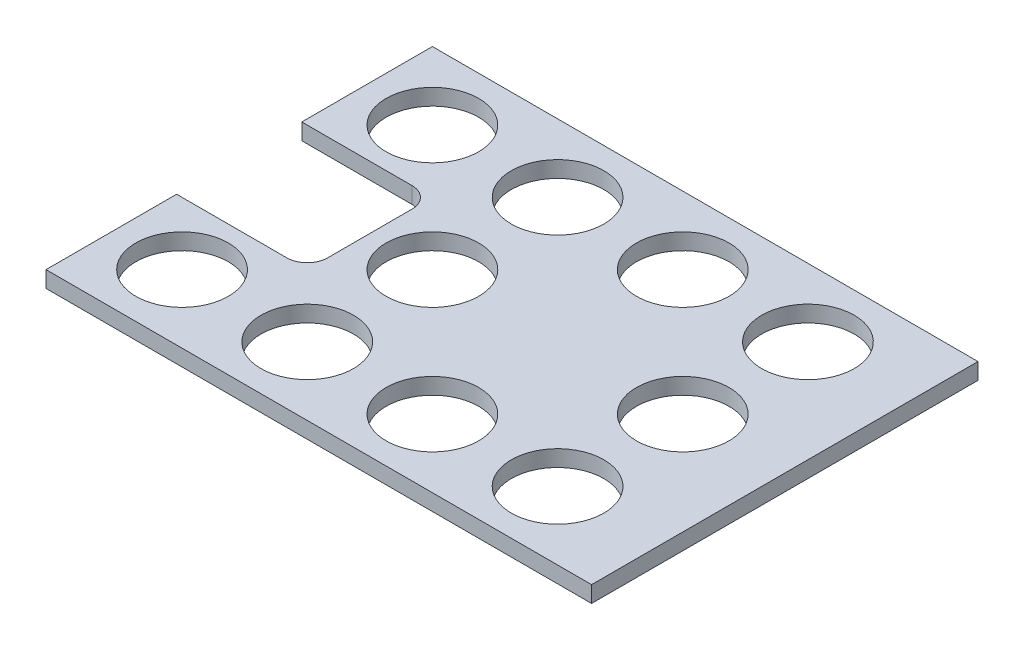
SolidWorks part; units mm, degrees
material "Pine"
ref_plane "Front Plane" through (0, 0, 0) normal (0, 0, 1) x (1, 0, 0)
ref_plane "Top Plane" through (0, 0, 0) normal (0, 1, 0) x (1, 0, 0)
ref_plane "Right Plane" through (0, 0, 0) normal (1, 0, 0) x (0, 0, -1)
sketch "Sketch1" plane through (0, 0, 0) normal (0, 1, 0) x (1, 0, 0)
  line L0 (50, 50) -> (268.076, 50) construction
  line L1 (0, 0) -> (401, 0)
  line L2 (0, 0) -> (0, 284)
  line L3 (0, 284) -> (401, 284)
  line L4 (401, 0) -> (401, 284)
  line L6 (0, 188) -> (81, 188)
  line L7 (0, 188) -> (0, 96)
  line L8 (0, 96) -> (81, 96)
  line L9 (96, 173) -> (96, 111)
  circle A0 centre (50, 50) radius 34
  circle A1 centre (50, 234) radius 34
  arc A2 (81, 96) -> (96, 111) centre (81, 111) ccw
  arc A3 (81, 188) -> (96, 173) centre (81, 173) cw
  circle A4 centre (142, 142) radius 34
  circle A5 centre (326, 142) radius 34
  point P21 (40.5, 96)
  point P22 (96, 142)
  dimension "D2" = 68
  dimension "D9" = 15
  dimension "D1" = 50
  dimension "D3" = 401
  dimension "height" = 284
  dimension "middle" = 142
  dimension "D12" = 142
  dimension "D4" = 92
  dimension "D10" = 96
  dimension "D8" = 96
  dimension "D7" = 50
  dimension "D11" = 46
  dimension "D6" = 46
  dimension "D5" = 46
  dimension "D13" = 184
extrude "Boss-Extrude1" add sketch "Sketch1" along normal blind 12 contours L2 L3 L4 L1
extrude "Cut-Extrude1" cut sketch "Sketch1<3>" along normal up to surface (12 mm away) contours A0 | A1 up to face at (200.5, 12, -142)
sketch "Sketch1<3>" plane through (0, 0, 0) normal (0, 1, 0) x (1, 0, 0) same geometry as "Sketch1"
pattern_linear "LPattern1" count 4 spacing 92 along (1, 0, 0) of "Cut-Extrude1"
extrude "Cut-Extrude3" cut sketch "Sketch1<4>" along normal up to surface (12 mm away) contours A3 L6 L2 L8 A2 L9 | A4 | A5 region at (47.5064, 0, -142) region at (142, 0, -142) region at (326, 0, -142) up to face at (326, 12, -16)
sketch "Sketch1<4>" plane through (0, 0, 0) normal (0, 1, 0) x (1, 0, 0) same geometry as "Sketch1"
equation "\"LENGTH\" = 1000mm"
equation "\"PLY\"= 12mm"
equation "\"D1@Boss-Extrude1\"=\"PLY\""
equation "\"CENTER_BRACE_LENGTH\" = 393mm"
equation "\"D3@Sketch1\"=\"CENTER_BRACE_LENGTH\" + \"HOUSING_DEPTH\" * 2"
equation "\"WIDTH\" = 300mm"
equation "\"HEIGHT\" = 300mm"
equation "\"HOUSING_DEPTH\" = 4mm"
equation "\"PANEL_WIDTH\"= \"LENGTH\" - \"CENTER_BRACE_LENGTH\" * 2 - \"PLY\" * 4"
equation "\"PANEL_SMALL_HEIGHT\" = 70mm"
equation "\"PORT_WIDTH\" = 90mm"
equation "\"PORT_RADIUS\" = 15mm"
equation "\"PORT_BRACE_HEIGHT\" = 92mm"
equation "\"DOWEL_SIZE\" = 0.25in"
equation "\"DOWEL_OFFSET\" = 30mm"
equation "\"height@Sketch1\" = \"HEIGHT\" - \"PLY\" * 2 + \"HOUSING_DEPTH\" * 2"
equation "\"middle@Sketch1\" = \"height@Sketch1\" / 2"
equation "\"D12@Sketch1\" = \"middle@Sketch1\""
equation "\"D4@Sketch1\"=\"PORT_BRACE_HEIGHT\""
equation "\"D10@Sketch1\"=\"height@Sketch1\" / 2 - \"PORT_BRACE_HEIGHT\" / 2"
equation "\"D8@Sketch1\"=\"PORT_BRACE_HEIGHT\" + \"HOUSING_DEPTH\""
equation "\"cut_out_offset\"= 46mm"
equation "\"D7@Sketch1\"=\"cut_out_offset\" + \"HOUSING_DEPTH\""
equation "\"D1@Sketch1\"=\"cut_out_offset\" + \"HOUSING_DEPTH\""
equation "\"D11@Sketch1\"=\"cut_out_offset\""
equation "\"D6@Sketch1\"=\"cut_out_offset\""
equation "\"D5@Sketch1\"=\"cut_out_offset\""
equation "\"D13@Sketch1\"=\"cut_out_offset\" * 4"
equation "\"D3@LPattern1\"=\"cut_out_offset\" * 2"
